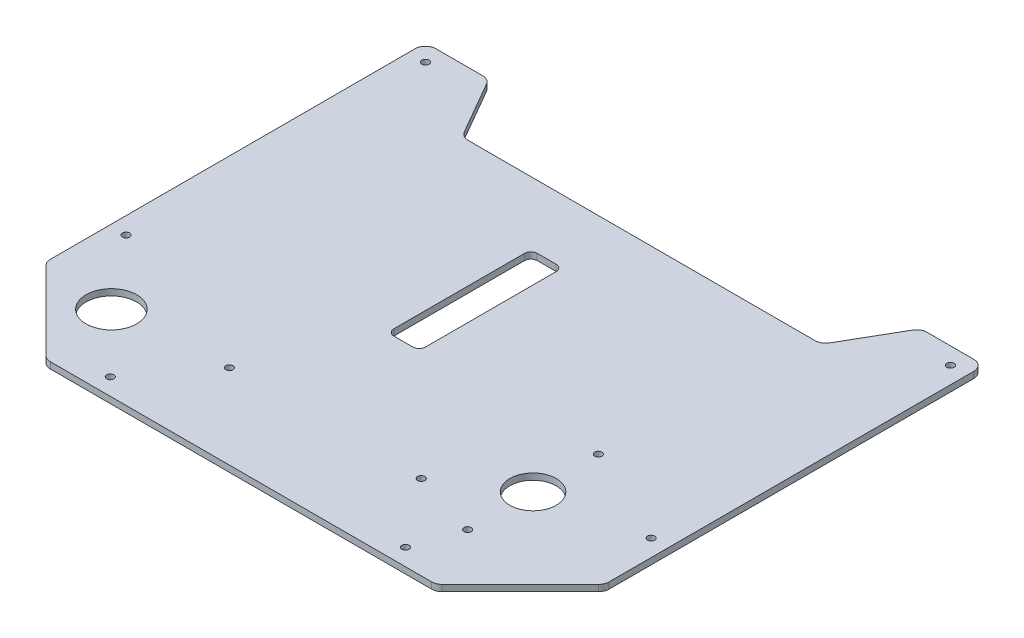
SolidWorks part; units mm, degrees
material "Acier non allié"
ref_plane "Front" through (0, 0, 0) normal (0, 0, 1) x (1, 0, 0)
ref_plane "Top" through (0, 0, 0) normal (0, 1, 0) x (1, 0, 0)
ref_plane "Right" through (0, 0, 0) normal (1, 0, 0) x (0, 0, -1)
sketch "Esquisse1" plane through (0, 0, 0) normal (0, 1, 0) x (1, 0, 0)
  line L0 (0, 0) -> (0, 1919.0564) construction
  line L1 (-92.5, 0) -> (92.5, 0)
  line L2 (92.5, 0) -> (132.5, 40)
  line L3 (132.5, 40) -> (132.5, 220)
  line L4 (132.5, 220) -> (102.5, 220)
  line L5 (102.5, 220) -> (85.1795, 190)
  line L6 (85.1795, 190) -> (-85.1795, 190)
  line L7 (-102.5, 220) -> (-85.1795, 190)
  line L8 (-132.5, 220) -> (-102.5, 220)
  line L9 (-132.5, 40) -> (-132.5, 220)
  line L10 (-92.5, 0) -> (-132.5, 40)
  point P12 (0, 190)
  dimension "D1" = 132.5
  dimension "D2" = 220
  dimension "D3" = 30
  dimension "D4" = 30
  dimension "D5" = 40
  dimension "D6" = 40
  dimension "D7" = 60
extrude "Boss.-Extru.1" add sketch "Esquisse1" along normal blind 3
fillet "Congé1" radius 5 10 edges at (132.5, 1.5, -220) (102.5, 1.5, -220) (85.1795, 1.5, -190) (-85.1795, 1.5, -190) (-102.5, 1.5, -220) (-132.5, 1.5, -220) (-132.5, 1.5, -40) (-92.5, 1.5, 0) (92.5, 1.5, 0) (132.5, 1.5, -40)
sketch "Esquisse2" plane through (0, 0, 0) normal (0, -1, 0) x (1, 0, 0)
  line L0 (0, 0) -> (0, -330.9968) construction
  line L1 (-90.4289, 0) -> (90.4289, 0) construction
  line L2 (-105.3868, -220) -> (-127.5, -220) construction
  line L3 (-132.5, -215) -> (-132.5, -42.0711) construction
  circle A0 centre (-70, -8) radius 1
  circle A1 centre (-124.5, -70) radius 1
  circle A2 centre (-124.5, -212) radius 1
  circle A3 centre (124.5, -212) radius 1
  circle A4 centre (124.5, -70) radius 1
  circle A5 centre (70, -8) radius 1
  dimension "D3" = 2
  dimension "D6" = 2
  dimension "D9" = 2
  dimension "D1" = 70
  dimension "D2" = 8
  dimension "D4" = 124.5
  dimension "D5" = 70
  dimension "D7" = 8
  dimension "D8" = 8
extrude "Enlèv. mat.-Extru.1" cut sketch "Esquisse2" against normal through all
hole_wizard "Dégagement M31" positions "Esquisse3" profile "Esquisse4" hole size "M3" standard "ISO" end condition through all
sketch "Esquisse3" plane through (0, 0, 0) normal (0, -1, 0) x (-1, 0, 0)
  point P0 (-70, 8)
  point P3 (-124.5, 70)
  point P6 (-124.5, 212)
  point P9 (124.5, 212)
  point P12 (124.5, 70)
  point P15 (70, 8)
sketch "Esquisse4" plane through (70, 0, -8) normal (1, 0, 0) x (0, 0, -1)
  line L0 (0, 0) -> (0, 3)
  line L1 (0, 3) -> (1.7, 3)
  line L2 (1.7, 3) -> (1.7, 0)
  line L5 (1.7, 0) -> (0, 0)
  line L11 (0, -6.35) -> (0, 107.95) construction
  dimension "Diamètre du perçage jusqu'au prochain" = 3.4
  dimension "Profondeur du perçage jusqu'au prochain" = 3
sketch "Esquisse5" plane through (0, 0, 0) normal (0, -1, 0) x (1, 0, 0)
  line L6 (132.5, -42.0711) -> (132.5, -215) construction
  line L7 (77.5, -92) -> (77.5, -30) construction
  line L20 (-132.5, -215) -> (-132.5, -42.0711) construction
  line L21 (-90.4289, 0) -> (90.4289, 0) construction
  line L22 (-105.3868, -220) -> (-127.5, -220) construction
  line L23 (-22.5, -160) -> (-7.5, -160)
  line L24 (-22.5, -160) -> (-22.5, -92)
  line L25 (-22.5, -92) -> (-7.5, -92)
  line L26 (-7.5, -160) -> (-7.5, -92)
  line L27 (-45.5, -40) -> (45.5, -40) construction
  circle A0 centre (-97.5, -36) radius 12
  circle A1 centre (-45.5, -40) radius 1.5
  circle A2 centre (45.5, -40) radius 1.5
  circle A3 centre (77.5, -61) radius 11
  circle A4 centre (77.5, -92) radius 1.5
  circle A5 centre (77.5, -30) radius 1.5
  point P8 (77.5, -61)
  point P35 (-22.5, -126)
  dimension "D10" = 24
  dimension "D15" = 3
  dimension "D16" = 3
  dimension "D2" = 22
  dimension "D6" = 3
  dimension "D7" = 3
  dimension "D3" = 55
  dimension "D4" = 61
  dimension "D5" = 62
  dimension "D8" = 35
  dimension "D9" = 36
  dimension "D11" = 60
  dimension "D12" = 68
  dimension "D13" = 110
  dimension "D14" = 15
  dimension "D17" = 91
  dimension "D18" = 40
  dimension "D19" = 87
extrude "Enlèv. mat.-Extru.2" cut sketch "Esquisse5" against normal through all
fillet "Congé2" radius 3 4 edges at (-22.5, 1.5, -92) (-7.5, 1.5, -92) (-7.5, 1.5, -160) (-22.5, 1.5, -160)
hole_wizard "Dégagement M32" positions "Esquisse6" profile "Esquisse7" hole size "M3" standard "ISO" end condition up to next
sketch "Esquisse6" plane through (0, 3, 0) normal (0, 1, 0) x (1, 0, 0)
  point P0 (-45.5, 40)
  point P3 (45.5, 40)
  point P7 (77.5, 92)
  point P10 (77.5, 30)
sketch "Esquisse7" plane through (-45.5, 3, -40) normal (1, 0, 0) x (0, 0, 1)
  line L0 (0, 0) -> (0, 3)
  line L1 (0, 3) -> (1.7, 3)
  line L2 (1.7, 3) -> (1.7, 0)
  line L5 (1.7, 0) -> (0, 0)
  line L11 (0, -6.35) -> (0, 107.95) construction
  dimension "Diamètre du perçage jusqu'au prochain" = 3.4
  dimension "Profondeur du perçage jusqu'au prochain" = 3
equation "\"WIDTH\"= 300mm'Total width of the robot"
equation "\"LENGTH\"= 220mm'Total length of the robot"
equation "\"CUT_DEPTH\"= 45mm'Depth of the cut on the edges of the plate"
equation "\"Plate_th\"= 3mm'Thickness of the plate"
equation "\"D1\"= \"Plate_th\""
